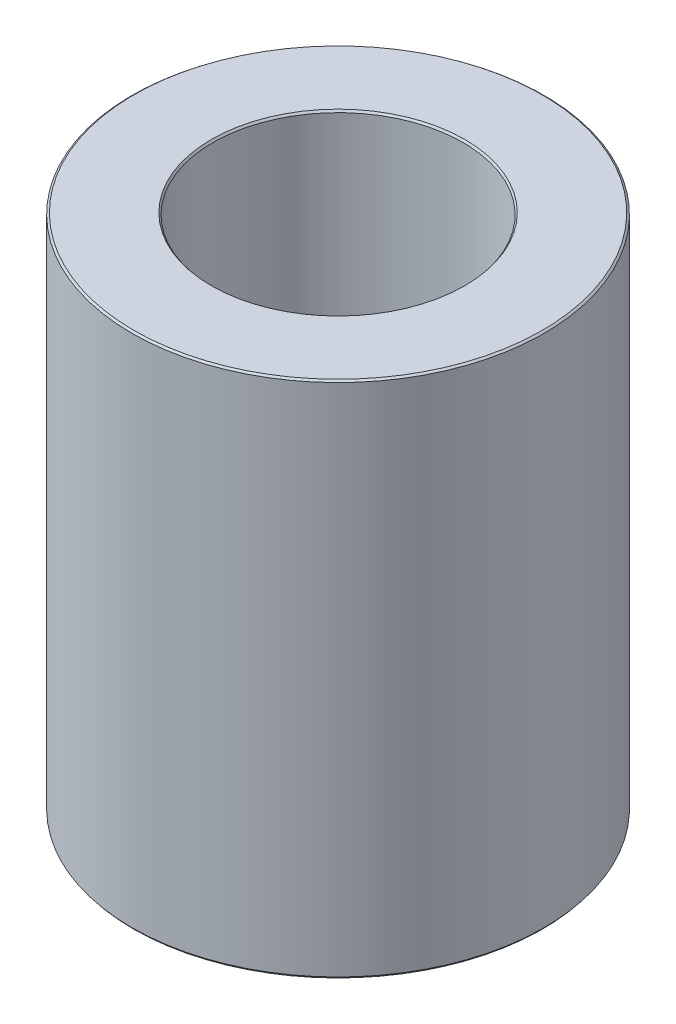
SolidWorks part; units mm, degrees
ref_plane "Front Plane" through (0, 0, 0) normal (0, 0, 1) x (1, 0, 0)
ref_plane "Top Plane" through (0, 0, 0) normal (0, 1, 0) x (1, 0, 0)
ref_plane "Right Plane" through (0, 0, 0) normal (1, 0, 0) x (0, 0, -1)
sketch "Sketch1" plane through (0, 0, 0) normal (0, 1, 0) x (1, 0, 0)
  circle A0 centre (0, 0) radius 50
  dimension "SLEEVE_OD" = 100
extrude "Boss-Extrude1" add sketch "Sketch1" along normal blind 125.7447
sketch "Sketch2" plane through (0, 0, 0) normal (0, 1, 0) x (1, 0, 0)
  circle A0 centre (0, 0) radius 30.381
  dimension "BORE_D" = 60.762
extrude "Cut-Extrude1" cut sketch "Sketch2" along normal through all
chamfer "Chamfer1" distance 0.3673 angle 52.116 4 edges at (0, 125.7447, 30.381) (0, 0, 30.381) (0, 0, 50) (0, 125.7447, 50) first distance on face at (0, 125.7447, 30.381) first distance on face at (0, 0, 30.381) first distance on face at (0, 125.7447, 50)
